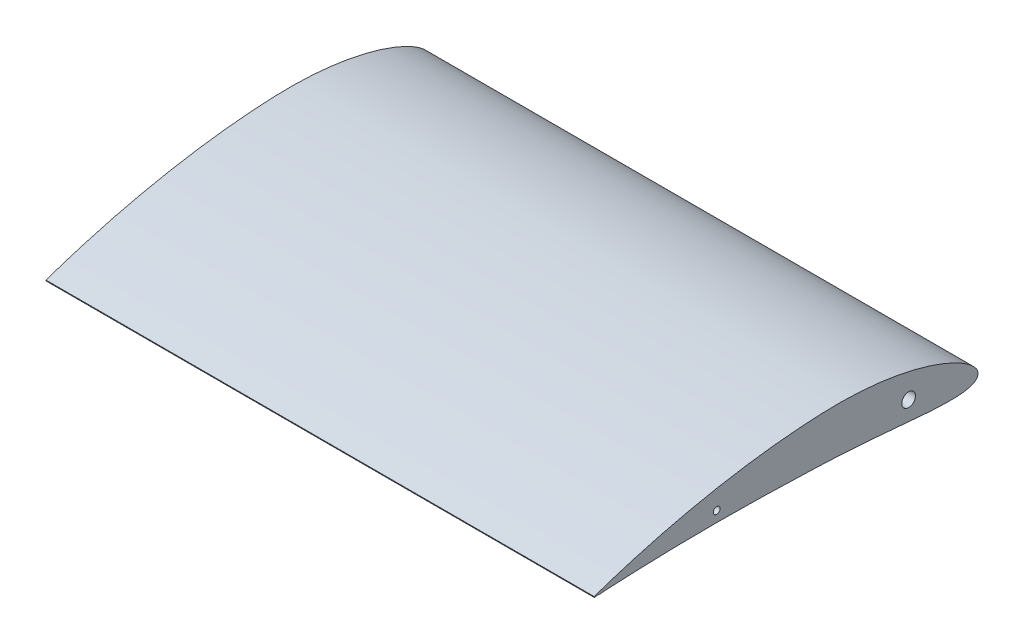
SolidWorks part; units mm, degrees
material "Thornel Mat VMA Foam Core"
ref_plane "Front Plane" through (0, 0, 0) normal (0, 0, 1) x (1, 0, 0)
ref_plane "Top Plane" through (0, 0, 0) normal (0, 1, 0) x (1, 0, 0)
ref_plane "Right Plane" through (0, 0, 0) normal (1, 0, 0) x (0, 0, -1)
curve "Curve1"
  spline degree 3 poles (0, 0.0012, 1.0003) (0, 0.0015, 0.9994) (0, 0.0028, 0.9958) (0, 0.0055, 0.9879) (0, 0.0099, 0.9747) (0, 0.0159, 0.9565) (0, 0.0233, 0.9333) (0, 0.0318, 0.9054) (0, 0.0411, 0.8731) (0, 0.051, 0.8366) (0, 0.0612, 0.7964) (0, 0.0713, 0.7528) (0, 0.0811, 0.7063) (0, 0.0903, 0.6574) (0, 0.0985, 0.6067) (0, 0.1057, 0.5546) (0, 0.1115, 0.5018) (0, 0.1158, 0.4488) (0, 0.1186, 0.3959) (0, 0.1189, 0.3436) (0, 0.1164, 0.2927) (0, 0.1112, 0.2442) (0, 0.1037, 0.1988) (0, 0.0942, 0.157) (0, 0.0831, 0.1194) (0, 0.0711, 0.0865) (0, 0.0584, 0.0585) (0, 0.0457, 0.0357) (0, 0.0334, 0.0184) (0, 0.0218, 0.0064) (0, 0.0108, -0.0005) (0, -0.0003, -0.0011) (0, -0.0092, 0.0055) (0, -0.0148, 0.017) (0, -0.0185, 0.0329) (0, -0.0204, 0.0533) (0, -0.0208, 0.0781) (0, -0.0198, 0.107) (0, -0.0176, 0.1398) (0, -0.0147, 0.176) (0, -0.0111, 0.2153) (0, -0.0074, 0.2574) (0, -0.0037, 0.3019) (0, -0.0005, 0.3484) (0, 0.002, 0.397) (0, 0.0037, 0.4471) (0, 0.0055, 0.4983) (0, 0.0069, 0.5496) (0, 0.0079, 0.6006) (0, 0.0085, 0.6505) (0, 0.0086, 0.699) (0, 0.0083, 0.7455) (0, 0.0076, 0.7894) (0, 0.0065, 0.8302) (0, 0.0053, 0.8675) (0, 0.0039, 0.9007) (0, 0.0027, 0.9296) (0, 0.0013, 0.9539) (0, 0.0006, 0.9727) (0, -0.0011, 0.9872) (0, 0, 0.9944) (0, -0.002, 0.9999) (0, -0.0005, 1) (0, 0, 1) knots 0 0 0 0 0.001372 0.005465 0.012235 0.021602 0.033461 0.047671 0.064081 0.082496 0.102719 0.124527 0.147676 0.171913 0.196978 0.222597 0.248497 0.274385 0.300041 0.32569 0.350525 0.37428 0.396711 0.417577 0.436654 0.453744 0.46868 0.481329 0.491631 0.499616 0.505546 0.510185 0.514824 0.520702 0.528516 0.538466 0.550543 0.564643 0.580638 0.598345 0.617584 0.638174 0.659922 0.682632 0.706121 0.730727 0.7557 0.780732 0.805564 0.829932 0.85357 0.876213 0.89761 0.917519 0.935698 0.951943 0.966047 0.97784 0.987174 0.993932 0.998018 0.999386 1 1 1 1
sketch "Sketch1" plane through (0, 0, 0) normal (1, 0, 0) x (0, 0, -1)
  line L0 (-354.7873, -0.0303) -> (-354.8762, 0.4104)
  line L1 (-354.7873, -0.0303) -> (0.8093, 1.5275) construction
  line L2 (0.8093, 1.5275) -> (0.7921, 5.4415) construction
  spline S1 degree 3 poles (-354.8762, 0.4104) (-354.5599, 0.5194) (-353.2997, 0.9536) (-350.4787, 1.9271) (-345.801, 3.4978) (-336.0241, 6.7216) (-319.6545, 11.7989) (-300.5983, 17.1306) (-282.4229, 21.7243) (-261.1758, 26.6516) (-238.6223, 31.1455) (-208.7748, 36.0048) (-183.9617, 39.0905) (-158.9023, 41.1132) (-140.0967, 42.1114) (-121.5167, 42.2289) (-103.4222, 41.3211) (-86.1884, 39.4787) (-70.0435, 36.8105) (-55.1998, 33.4329) (-41.8434, 29.5109) (-30.1305, 25.2201) (-20.187, 20.7343) (-12.1072, 16.2263) (-5.9269, 11.8553) (-1.6792, 7.7165) (0.7658, 3.7968) (0.9875, -0.1483) (-1.3511, -3.3089) (-5.4508, -5.2881) (-11.0873, -6.5875) (-18.3491, -7.2685) (-27.1638, -7.4049) (-37.4471, -7.0538) (-49.0831, -6.3019) (-61.9524, -5.238) (-75.9299, -3.9839) (-96.4067, -2.1536) (-117.9372, -0.4584) (-140.4848, 0.6745) (-158.2965, 1.2867) (-176.4839, 1.9179) (-200.672, 2.5862) (-224.5411, 2.9791) (-247.8302, 3.0285) (-264.3373, 2.9074) (-279.9331, 2.6564) (-294.438, 2.2829) (-307.6819, 1.8521) (-319.5134, 1.3711) (-329.7674, 0.9129) (-338.3889, 0.4268) (-345.077, 0.1915) (-350.2276, -0.4064) (-352.7802, -0.0354) (-354.7446, -0.7581) (-354.7772, -0.2025) (-354.7873, -0.0303) knots 0 0 0 0 0.001372 0.005465 0.012235 0.021602 0.047671 0.082496 0.102719 0.124527 0.171913 0.196978 0.248497 0.274385 0.300041 0.32569 0.350525 0.37428 0.396711 0.417577 0.436654 0.453744 0.46868 0.481329 0.491631 0.499616 0.505546 0.510185 0.514824 0.520702 0.528516 0.538466 0.550543 0.564643 0.580638 0.598345 0.617584 0.638174 0.682632 0.706121 0.730727 0.7557 0.780732 0.829932 0.85357 0.876213 0.89761 0.917519 0.935698 0.951943 0.966047 0.97784 0.987174 0.993932 0.998018 0.999386 1 1 1 1
  dimension "D1" = 355.6
extrude "Boss-Extrude1" add sketch "Sketch1" along normal blind 254 and the other way blind 254
sketch "Sketch2" plane through (-254, 0, 0) normal (-1, 0, 0) x (0, 0, 1)
  line L0 (195.725, 0) -> (-195.725, 0) construction
  line L1 (0, -27.2986) -> (0, 27.2986) construction
  circle A0 centre (63.5, 12.7) radius 6.35
  dimension "D1" = 12.7
  dimension "D2" = 12.7
  dimension "D3" = 63.5
extrude "Cut-Extrude1" cut sketch "Sketch2" against normal blind 101.6
mirror "Mirror1" about plane through (0, 0, 0) normal (1, 0, 0) of "Cut-Extrude1"
sketch "Sketch3" plane through (-254, 0, 0) normal (-1, 0, 0) x (0, 0, 1)
  line L0 (195.725, 0) -> (-195.725, 0) construction
  line L1 (0, -27.2986) -> (0, 27.2986) construction
  circle A0 centre (241.3, 12.7) radius 3.175
  point P4 (0, 0)
  dimension "D1" = 6.35
  dimension "D2" = 12.7
  dimension "D3" = 241.3
extrude "Cut-Extrude2" cut sketch "Sketch3" against normal blind 127
mirror "Mirror2" about plane through (0, 0, 0) normal (1, 0, 0) of "Cut-Extrude2"
